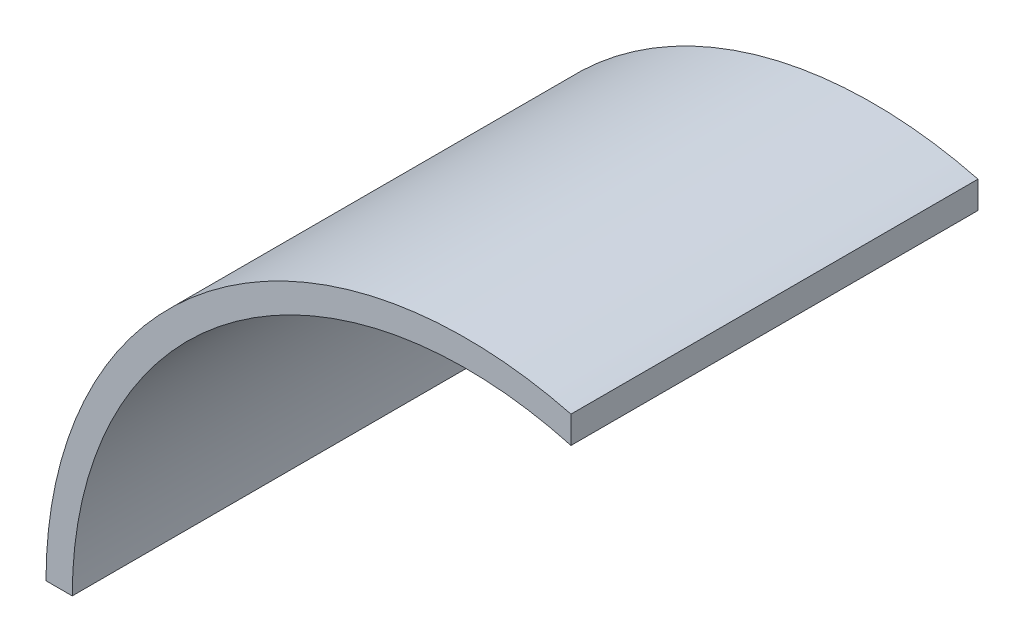
SolidWorks part; units mm, degrees
material "201 Annealed Stainless Steel (SS)"
ref_plane "Front Plane" through (0, 0, 0) normal (0, 0, 1) x (1, 0, 0)
ref_plane "Top Plane" through (0, 0, 0) normal (0, 1, 0) x (1, 0, 0)
ref_plane "Right Plane" through (0, 0, 0) normal (1, 0, 0) x (0, 0, -1)
sketch "Sketch1" plane through (0, 0, 0) normal (0, 0, 1) x (1, 0, 0)
  line L0 (0, 0) -> (0, -160) construction
  line L2 (0, 0) -> (101.5936, 0) construction
  line L3 (39.9343, 113.7839) -> (39.9343, -22.985) construction
  line L5 (39.9343, 154.9363) -> (39.9343, 144.5865)
  line L7 (0, 0) -> (-150, 0) construction
  line L25 (-160, 0) -> (-150, 0)
  circle A0 centre (0, 0) radius 150 construction
  circle A1 centre (0, 0) radius 160 construction
  arc A2 (-150, 0) -> (39.9343, 144.5865) centre (0, 0) cw
  arc A3 (-160, 0) -> (39.9343, 154.9363) centre (0, 0) cw
  dimension "D1" = 300
  dimension "D2" = 320
  dimension "D3" = 39.9343
extrude "Inner Ring - Left Side" add sketch "Sketch1" along normal blind 155
